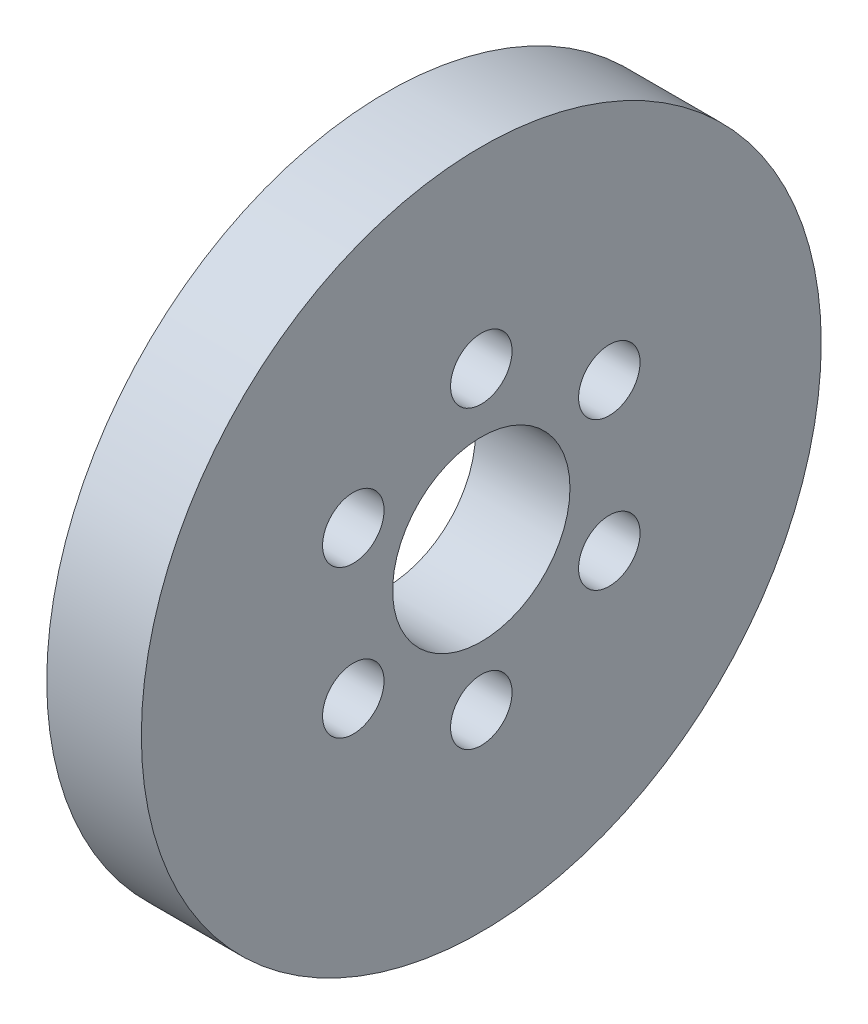
SolidWorks part; units mm, degrees
ref_plane "Front Plane" through (0, 0, 0) normal (0, 0, 1) x (1, 0, 0)
ref_plane "Top Plane" through (0, 0, 0) normal (0, 1, 0) x (1, 0, 0)
ref_plane "Right Plane" through (0, 0, 0) normal (1, 0, 0) x (0, 0, -1)
sketch "Sketch1" plane through (0, 0, 0) normal (1, 0, 0) x (0, 0, -1)
  circle A0 centre (0, 0) radius 18.2562
  dimension "D1" = 36.5125
extrude "Boss-Extrude1" add sketch "Sketch1" along normal blind 5.08
hole_wizard "#4 Clearance Hole1" positions "Sketch3" profile "Sketch2" hole size "#4" standard "Progressive" end condition through all
sketch "Sketch3" plane through (5.08, 0, 0) normal (1, 0, 0) x (0, 0, -1)
  line L0 (0, 0) -> (0, 7.9375) construction
  line L1 (0, 0) -> (6.8741, 3.9687) construction
  line L2 (0, 0) -> (6.8741, -3.9688) construction
  line L3 (0, 0) -> (0, -7.9375) construction
  line L4 (0, 0) -> (-6.8741, -3.9687) construction
  line L5 (0, 0) -> (-6.8741, 3.9688) construction
  point P5 (0, 7.9375)
  point P16 (6.8741, 3.9687)
  point P17 (6.8741, -3.9688)
  point P18 (0, -7.9375)
  point P19 (-6.8741, -3.9687)
  point P20 (-6.8741, 3.9688)
  point P21 (0, 0)
  dimension "D1" = 7.9375
  dimension "D2" = 6
sketch "Sketch2" plane through (5.08, 7.9375, 0) normal (0, 1, 0) x (0, 0, -1)
  line L0 (0, 0) -> (0, 5.08)
  line L1 (0, 5.08) -> (1.651, 5.08)
  line L2 (1.651, 5.08) -> (1.651, 0)
  line L5 (1.651, 0) -> (0, 0)
  line L11 (0, -6.35) -> (0, 107.95) construction
  dimension "Thru Hole Dia." = 3.302
  dimension "Thru Hole Depth" = 5.08
hole_wizard "#4 Clearance Hole2" positions "Sketch5" profile "Sketch4" hole size "#4" standard "Progressive"
sketch "Sketch5" plane through (5.08, 0, 0) normal (1, 0, 0) x (0, 0, -1)
  point P0 (0, 0)
sketch "Sketch4" plane through (5.08, 0, 0) normal (0, 1, 0) x (0, 0, -1)
  line L0 (0, 0) -> (0, 60.0116)
  line L1 (0, 60.0116) -> (4.7625, 57.15)
  line L2 (4.7625, 57.15) -> (4.7625, 0)
  line L5 (4.7625, 0) -> (0, 0)
  line L10 (0, 60.0116) -> (-4.7625, 57.15) construction
  line L11 (0, -6.35) -> (0, 107.95) construction
  dimension "Hole Dia." = 9.525
  dimension "Hole Depth" = 57.15
  dimension "Drill Angle" = 118
